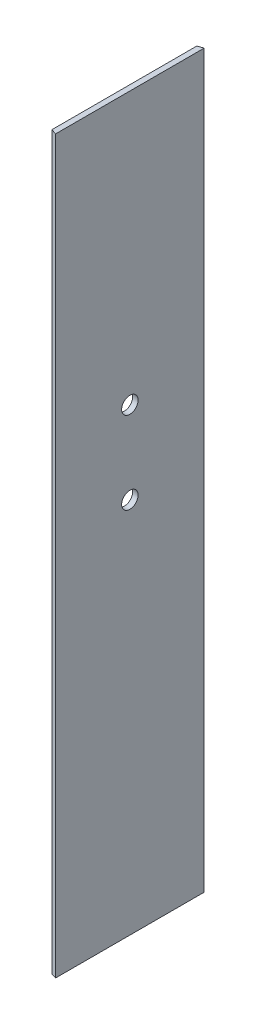
SolidWorks part; units mm, degrees
ref_plane "Спереди" through (0, 0, 0) normal (0, 0, 1) x (1, 0, 0)
ref_plane "Сверху" through (0, 0, 0) normal (0, 1, 0) x (1, 0, 0)
ref_plane "Справа" through (0, 0, 0) normal (1, 0, 0) x (0, 0, -1)
sketch "Эскиз1" plane through (0, 0, 0) normal (0, 1, 0) x (1, 0, 0)
  line L0 (1.0096, -0.8302) -> (1.0096, -106.5801)
  line L1 (1.0096, -106.5801) -> (5.0096, -107.836)
  line L2 (5.0096, -107.836) -> (5.0096, 0.4988)
  line L3 (5.0096, 0.4988) -> (1.0096, -0.8302)
  dimension "D1" = 4
extrude "Вытянуть1" add sketch "Эскиз1" along normal up to surface (533.2137 mm away)
sketch "Эскиз2" plane through (5.0096, 0, 0) normal (1, 0, 0) x (0, 0, -1)
  line L0 (-53.8283, 532.7311) -> (-53.8283, 555.5207) construction
  line L9 (-86.4672, 300.9556) -> (-23.7172, 300.9556)
  line L10 (-91.4672, 295.9556) -> (-91.4672, 145.9556)
  line L11 (-86.4672, 140.9556) -> (-23.7172, 140.9556)
  line L12 (-18.7172, 295.9556) -> (-18.7172, 145.9556)
  arc A4 (-86.4672, 300.9556) -> (-91.4672, 295.9556) centre (-86.4672, 295.9556) ccw
  arc A5 (-18.7172, 295.9556) -> (-23.7172, 300.9556) centre (-23.7172, 295.9556) ccw
  arc A6 (-23.7172, 140.9556) -> (-18.7172, 145.9556) centre (-23.7172, 145.9556) ccw
  arc A7 (-91.4672, 145.9556) -> (-86.4672, 140.9556) centre (-86.4672, 145.9556) ccw
sketch "Sketch1" plane through (5.0096, 0, 0) normal (1, 0, 0) x (0, 0, -1)
  line L0 (-53.6686, 503.3764) -> (-53.6686, 609.6314) construction
  line L2 (-107.836, 0) -> (0.4988, 0) construction
  circle A0 centre (-53.6686, 335) radius 6
  circle A1 centre (-53.6686, 275) radius 6
  dimension "D1" = 275
  dimension "D2" = 335
extrude "Cut-Extrude1" cut sketch "Sketch1" against normal through all
